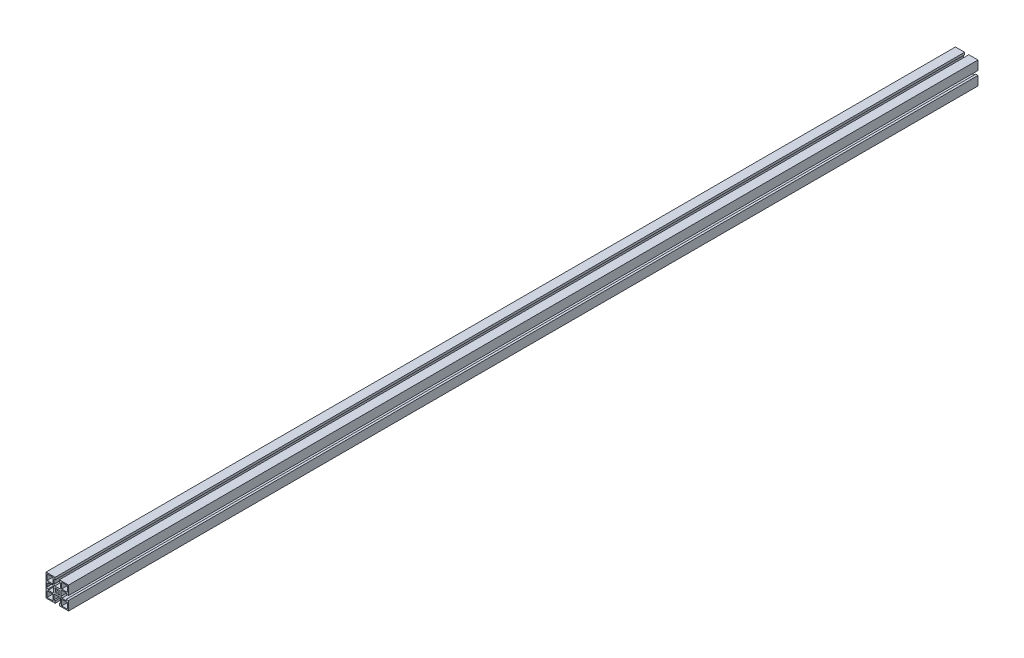
SolidWorks part; units mm, degrees
material "6061 Alloy"
ref_plane "Front Plane" through (0, 0, 0) normal (0, 0, 1) x (1, 0, 0)
ref_plane "Top Plane" through (0, 0, 0) normal (0, 1, 0) x (1, 0, 0)
ref_plane "Right Plane" through (0, 0, 0) normal (1, 0, 0) x (0, 0, -1)
sketch "Sketch1" plane through (0, 0, 0) normal (0, 0, 1) x (1, 0, 0)
  line L0 (-4.2495, 22.1993) -> (-4.2495, 22.4993)
  line L1 (-4.2495, 22.4993) -> (-4.2495, 22.1993)
  line L2 (4.2505, 22.1993) -> (4.2505, 22.4993)
  line L3 (4.2505, 22.4993) -> (4.2505, 22.1993)
  line L4 (-22.1995, 4.2493) -> (-22.4995, 4.2493)
  line L5 (-22.1995, -4.2507) -> (-22.4995, -4.2507)
  line L6 (-4.2495, -22.2007) -> (-4.2495, -22.5007)
  line L7 (4.2505, -22.2007) -> (4.2505, -22.5007)
  line L8 (-22.4995, -22.5007) -> (22.5005, -22.5007)
  line L9 (22.5005, -22.5007) -> (22.5005, 22.4993)
  line L10 (22.5005, 22.4993) -> (-22.4995, 22.4993)
  line L11 (-22.4995, 22.4993) -> (-22.4995, -22.5007)
  line L12 (22.2005, -4.2507) -> (22.5005, -4.2507)
  line L13 (22.2005, 4.2493) -> (22.5005, 4.2493)
  line L24 (-20.4995, -20.5007) -> (-20.4995, -8.8007)
  line L25 (-8.7996, -20.5007) -> (-20.4995, -20.5007)
  line L26 (-8.7996, -8.8007) -> (-8.7996, -20.5007)
  line L27 (-20.4995, -8.8007) -> (-8.7996, -8.8007)
  line L28 (8.8005, -20.5008) -> (8.8005, -8.8008)
  line L29 (20.5005, -20.5008) -> (8.8005, -20.5008)
  line L30 (20.5005, -8.8008) -> (20.5005, -20.5008)
  line L31 (8.8005, -8.8008) -> (20.5005, -8.8008)
  line L32 (20.5006, 8.7993) -> (8.8006, 8.7993)
  line L33 (20.5006, 20.4993) -> (20.5006, 8.7993)
  line L34 (8.8006, 20.4993) -> (20.5006, 20.4993)
  line L35 (8.8006, 8.7993) -> (8.8006, 20.4993)
  line L36 (-8.7995, 20.4993) -> (-8.7995, 8.7993)
  line L37 (-8.7995, 8.7993) -> (-20.4995, 8.7993)
  line L38 (-20.4995, 8.7993) -> (-20.4995, 20.4993)
  line L39 (-20.4995, 20.4993) -> (-8.7995, 20.4993)
  line L54 (-22.1995, -3.9507) -> (-21.7318, -3.483)
  line L55 (-22.1995, -4.2507) -> (-22.1995, -3.9507)
  line L56 (-17.9995, -4.2507) -> (-22.1995, -4.2507)
  line L57 (-17.9995, -6.8007) -> (-17.9995, -4.2507)
  line L58 (-9.1995, -6.8007) -> (-17.9995, -6.8007)
  line L59 (-7.1995, -4.8007) -> (-9.1995, -6.8007)
  line L60 (-7.1995, 4.7993) -> (-7.1995, -4.8007)
  line L61 (-9.1995, 6.7993) -> (-7.1995, 4.7993)
  line L62 (-17.9995, 6.7993) -> (-9.1995, 6.7993)
  line L63 (-17.9995, 4.2493) -> (-17.9995, 6.7993)
  line L64 (-22.1995, 4.2493) -> (-17.9995, 4.2493)
  line L65 (-22.1995, 3.9493) -> (-22.1995, 4.2493)
  line L66 (-21.7317, 3.4815) -> (-22.1995, 3.9493)
  line L67 (-20.9995, -1.7152) -> (-20.9995, 1.7137)
  line L82 (-6.7995, -18.0007) -> (-6.7995, -9.2007)
  line L83 (-4.2495, -18.0007) -> (-6.7995, -18.0007)
  line L84 (-4.2495, -22.2007) -> (-4.2495, -18.0007)
  line L85 (-3.9495, -22.2007) -> (-4.2495, -22.2007)
  line L86 (-3.4817, -21.733) -> (-3.9495, -22.2007)
  line L87 (1.715, -21.0007) -> (-1.7139, -21.0007)
  line L88 (3.9505, -22.2007) -> (3.4828, -21.733)
  line L89 (4.2505, -22.2007) -> (3.9505, -22.2007)
  line L90 (4.2505, -18.0007) -> (4.2505, -22.2007)
  line L91 (6.8005, -18.0007) -> (4.2505, -18.0007)
  line L92 (6.8005, -9.2007) -> (6.8005, -18.0007)
  line L93 (4.8005, -7.2007) -> (6.8005, -9.2007)
  line L94 (-4.7995, -7.2007) -> (4.8005, -7.2007)
  line L95 (-6.7995, -9.2007) -> (-4.7995, -7.2007)
  line L110 (7.2005, -4.8007) -> (7.2005, 4.7993)
  line L111 (9.2005, -6.8007) -> (7.2005, -4.8007)
  line L112 (18.0005, -6.8007) -> (9.2005, -6.8007)
  line L113 (18.0005, -4.2507) -> (18.0005, -6.8007)
  line L114 (22.2005, -4.2507) -> (18.0005, -4.2507)
  line L115 (22.2005, -3.9507) -> (22.2005, -4.2507)
  line L116 (21.7327, -3.4829) -> (22.2005, -3.9507)
  line L117 (21.0005, 1.7138) -> (21.0005, -1.7151)
  line L118 (22.2005, 3.9493) -> (21.7328, 3.4816)
  line L119 (22.2005, 4.2493) -> (22.2005, 3.9493)
  line L120 (18.0005, 4.2493) -> (22.2005, 4.2493)
  line L121 (18.0005, 6.7993) -> (18.0005, 4.2493)
  line L122 (9.2005, 6.7993) -> (18.0005, 6.7993)
  line L123 (7.2005, 4.7993) -> (9.2005, 6.7993)
  line L138 (-4.7995, 7.1993) -> (-6.7995, 9.1993)
  line L139 (4.8005, 7.1993) -> (-4.7995, 7.1993)
  line L140 (6.8005, 9.1993) -> (4.8005, 7.1993)
  line L141 (6.8005, 17.9993) -> (6.8005, 9.1993)
  line L142 (4.2505, 17.9993) -> (6.8005, 17.9993)
  line L143 (4.2505, 22.1993) -> (4.2505, 17.9993)
  line L144 (3.9505, 22.1993) -> (4.2505, 22.1993)
  line L145 (3.4828, 21.7316) -> (3.9505, 22.1993)
  line L146 (-1.7139, 20.9993) -> (1.715, 20.9993)
  line L147 (-3.9495, 22.1993) -> (-3.4817, 21.7315)
  line L148 (-4.2495, 22.1993) -> (-3.9495, 22.1993)
  line L149 (-4.2495, 17.9993) -> (-4.2495, 22.1993)
  line L150 (-6.7995, 17.9993) -> (-4.2495, 17.9993)
  line L151 (-6.7995, 9.1993) -> (-6.7995, 17.9993)
  line L164 (-4.5957, -3.1827) -> (-3.2622, -1.8492)
  line L165 (-3.1815, -4.5969) -> (-4.5957, -3.1827)
  line L166 (-1.848, -3.2635) -> (-3.1815, -4.5969)
  line L167 (3.1825, -4.5969) -> (1.849, -3.2635)
  line L168 (4.5967, -3.1827) -> (3.1825, -4.5969)
  line L169 (3.2633, -1.8492) -> (4.5967, -3.1827)
  line L170 (4.5967, 3.1813) -> (3.2633, 1.8478)
  line L171 (3.1825, 4.5955) -> (4.5967, 3.1813)
  line L172 (1.849, 3.262) -> (3.1825, 4.5955)
  line L173 (-3.1815, 4.5955) -> (-1.848, 3.262)
  line L174 (-4.5957, 3.1813) -> (-3.1815, 4.5955)
  line L175 (-3.2622, 1.8478) -> (-4.5957, 3.1813)
  arc A2 (-21.7318, -3.483) -> (-20.9995, -1.7152) centre (-23.4995, -1.7152) ccw
  arc A3 (-20.9995, 1.7137) -> (-21.7317, 3.4815) centre (-23.4995, 1.7137) ccw
  arc A6 (-1.7139, -21.0007) -> (-3.4817, -21.733) centre (-1.7139, -23.5007) ccw
  arc A7 (3.4828, -21.733) -> (1.715, -21.0007) centre (1.715, -23.5007) ccw
  arc A10 (21.0005, -1.7151) -> (21.7327, -3.4829) centre (23.5005, -1.7151) ccw
  arc A11 (21.7328, 3.4816) -> (21.0005, 1.7138) centre (23.5005, 1.7138) ccw
  arc A14 (1.715, 20.9993) -> (3.4828, 21.7316) centre (1.715, 23.4993) ccw
  arc A15 (-3.4817, 21.7315) -> (-1.7139, 20.9993) centre (-1.7139, 23.4993) ccw
  arc A20 (-1.848, -3.2635) -> (1.849, -3.2635) centre (0.0005, -0.0007) ccw
  arc A21 (3.2633, -1.8492) -> (3.2633, 1.8478) centre (0.0005, -0.0007) ccw
  arc A22 (1.849, 3.262) -> (-1.848, 3.262) centre (0.0005, -0.0007) ccw
  arc A23 (-3.2622, 1.8478) -> (-3.2622, -1.8492) centre (0.0005, -0.0007) ccw
extrude "Boss-Extrude1" add sketch "Sketch1" along normal blind 1816.1 contours L138 L151 L150 L149 L0 L10 L11 L4 L64 L63 L62 L61 L60 L59 L58 L57 L56 L5 L8 L6 L84 L83 L82 L95 L94 L93 L92 L91 L90 L7 L9 L12 L114 L113 L112 L111 L110 L123 L122 L121 L120 L13 L2 L143 L142 L141 L140 | L147 A15 L146 A14 L145 L144 L2 L10 L0 L148 | L67 A3 L66 L65 L4 L11 L5 L55 L54 A2 region at (-4.8859, 20.0993, 0) region at (0.0005, 21.8242, 0) region at (-21.8244, -0.0007, 0)
extrude "Cut-Extrude1" cut sketch "Sketch1<4>" along normal up to next contours L147 A15 L146 A14 L145 L144 L2 L10 L0 L148 region at (0.0005, 21.8242, 0)
sketch "Sketch1<4>" plane through (0, 0, 0) normal (0, 0, 1) x (1, 0, 0) same geometry as "Sketch1"
